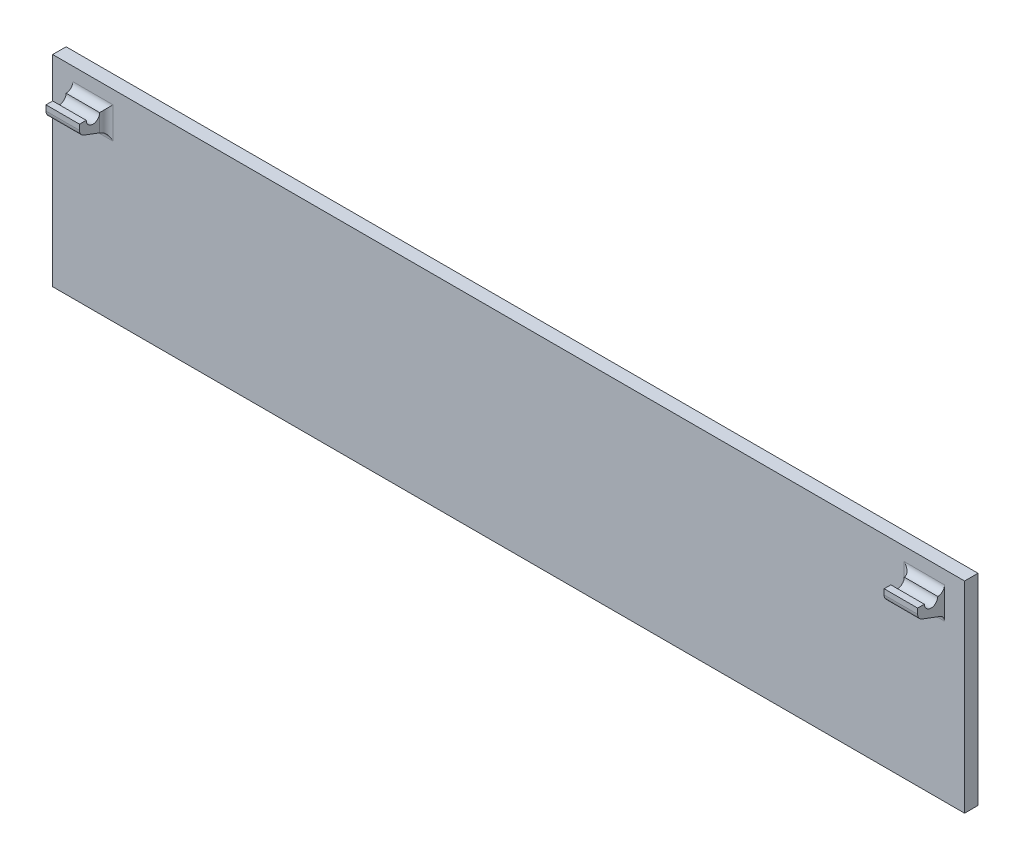
SolidWorks part; units mm, degrees
material "AISI 4340 Steel, annealed"
ref_plane "Front Plane" through (0, 0, 0) normal (0, 0, 1) x (1, 0, 0)
ref_plane "Top Plane" through (0, 0, 0) normal (0, 1, 0) x (1, 0, 0)
ref_plane "Right Plane" through (0, 0, 0) normal (1, 0, 0) x (0, 0, -1)
sketch "Sketch1" plane through (0, 0, 0) normal (0, 0, 1) x (1, 0, 0)
  line L1 (-340, 75) -> (340, 75)
  line L2 (-340, 75) -> (-340, -75)
  line L3 (-340, -75) -> (340, -75)
  line L4 (340, 75) -> (340, -75)
  line L5 (-340, 75) -> (340, -75) construction
  line L6 (-340, -75) -> (340, 75) construction
  point P0 (0, 0)
  dimension "D1" = 680
  dimension "D2" = 150
extrude "Vertical portion" add sketch "Sketch1" along normal blind 10
ref_plane "Plane1" through (325, 0, 0) normal (1, 0, 0) x (0, 0, -1)
sketch "Sketch4" plane through (325, 0, 0) normal (1, 0, 0) x (0, 0, -1)
  line L0 (-10, 75) -> (0, 75) construction
  line L1 (-10, 45) -> (-30, 52.5)
  line L2 (-15, 60) -> (-10, 60)
  line L3 (-10, -75) -> (-10, 75) construction
  line L4 (-10, 60) -> (-10, 55)
  line L5 (-10, 55) -> (-10, 45)
  line L6 (-10, 45) -> (-30, 45) construction
  line L7 (-30, 52.5) -> (-30, 60)
  line L8 (-30, 60) -> (-25, 60)
  line L9 (-30, 52.5) -> (-30, 45) construction
  line L10 (-10, -75) -> (-10, 75) construction
  arc A0 (-25, 60) -> (-15, 60) centre (-20, 60) ccw
  dimension "D1" = 10
  dimension "D6" = 15
  dimension "D2" = 10
  dimension "D3" = 10
  dimension "D4" = 5
  dimension "D5" = 20
extrude "Shaft adapter right" add sketch "Sketch4" against normal blind 25 contours L7 L8 A0 L2 L4 L5 L1
mirror "Shaft adapter left" about plane through (0, 0, 0) normal (1, 0, 0) of "Shaft adapter right"
fillet "Shaft adapter fillets" radius 5 8 edges at (-312.5, 52.5, 30) (312.5, 52.5, 30) (300, 52.5, 10) (-300, 52.5, 10) (-312.5, 45, 10) (312.5, 45, 10) (312.5, 60, 10) (-312.5, 60, 10)
sketch "Sketch5" plane through (0, 0, 0) normal (0, 0, -1) x (-1, 0, 0)
  line L0 (340, -75) -> (-340, -75) construction
  line L1 (-150, -75) -> (-50, -75)
  line L2 (-150, -75) -> (-150, -70)
  line L3 (-150, -70) -> (-50, -70)
  line L4 (-50, -75) -> (-50, -70)
  line L5 (0, 55) -> (0, -55) construction
  line L10 (50, -75) -> (50, -70)
  line L11 (150, -70) -> (50, -70)
  line L12 (150, -75) -> (150, -70)
  line L13 (150, -75) -> (50, -75)
  dimension "D1" = 50
  dimension "D2" = 100
  dimension "D3" = 5
extrude "Limit tab (prevents gate from getting pushed out of slot)" add sketch "Sketch5" along normal blind 10
fillet "Limit tab fillets" radius 5 6 edges at (-50, -72.5, 0) (-100, -70, 0) (-150, -72.5, 0) (50, -72.5, 0) (150, -72.5, 0) (100, -70, 0)
